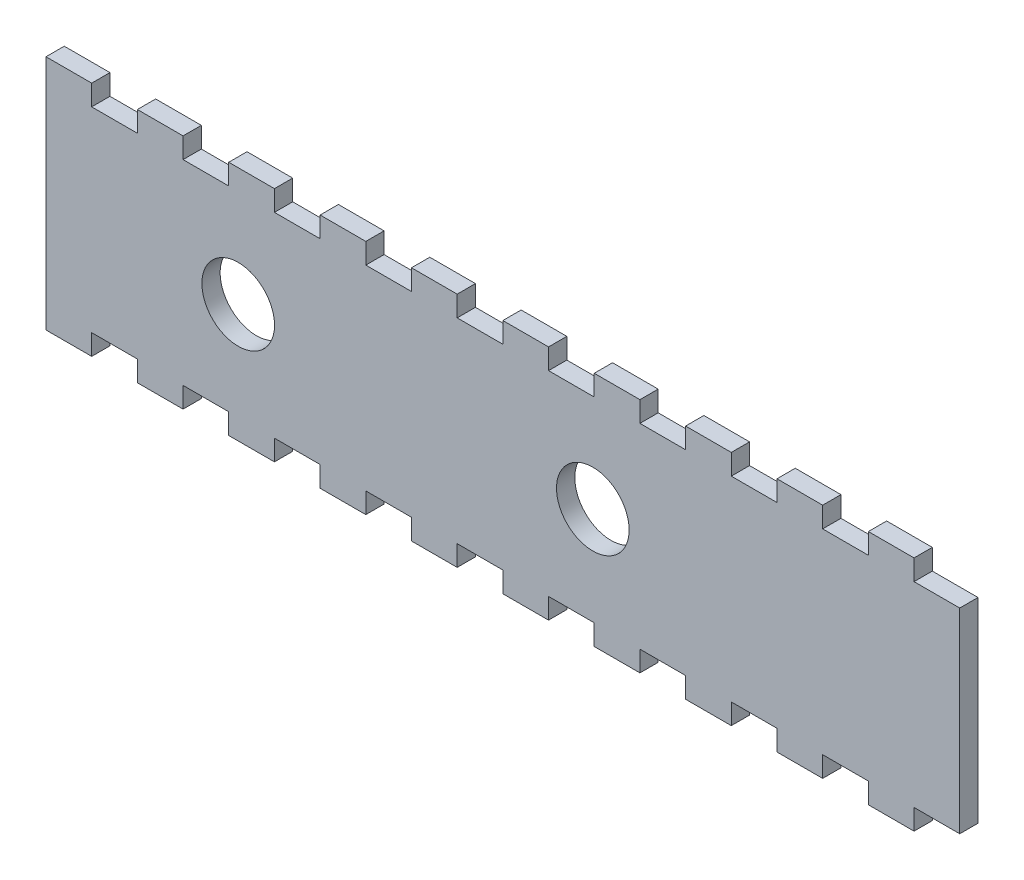
SolidWorks part; units mm, degrees
ref_plane "Front Plane" through (0, 0, 0) normal (0, 0, 1) x (1, 0, 0)
ref_plane "Top Plane" through (0, 0, 0) normal (0, 1, 0) x (1, 0, 0)
ref_plane "Right Plane" through (0, 0, 0) normal (1, 0, 0) x (0, 0, -1)
sketch "Sketch1" plane through (0, 0, 0) normal (0, 0, 1) x (1, 0, 0)
  line L0 (0, 10.7) -> (100, 10.7) construction
  line L1 (0, 0) -> (100, 0)
  line L2 (0, 0) -> (0, 21.4)
  line L3 (0, 21.4) -> (100, 21.4)
  line L4 (100, 0) -> (100, 21.4)
  line L5 (0, 21.4) -> (0, 23.65)
  line L6 (0, 23.65) -> (5, 23.65)
  line L7 (5, 23.65) -> (5, 21.4)
  line L8 (10, 23.65) -> (15, 23.65)
  line L9 (15, 23.65) -> (15, 21.4)
  line L10 (10, 21.4) -> (10, 23.65)
  line L11 (20, 23.65) -> (25, 23.65)
  line L12 (25, 23.65) -> (25, 21.4)
  line L13 (20, 21.4) -> (20, 23.65)
  line L14 (30, 23.65) -> (35, 23.65)
  line L15 (35, 23.65) -> (35, 21.4)
  line L16 (30, 21.4) -> (30, 23.65)
  line L17 (40, 23.65) -> (45, 23.65)
  line L18 (45, 23.65) -> (45, 21.4)
  line L19 (40, 21.4) -> (40, 23.65)
  line L20 (50, 23.65) -> (55, 23.65)
  line L21 (55, 23.65) -> (55, 21.4)
  line L22 (50, 21.4) -> (50, 23.65)
  line L23 (60, 23.65) -> (65, 23.65)
  line L24 (65, 23.65) -> (65, 21.4)
  line L25 (60, 21.4) -> (60, 23.65)
  line L26 (70, 23.65) -> (75, 23.65)
  line L27 (75, 23.65) -> (75, 21.4)
  line L28 (70, 21.4) -> (70, 23.65)
  line L29 (80, 23.65) -> (85, 23.65)
  line L30 (85, 23.65) -> (85, 21.4)
  line L31 (80, 21.4) -> (80, 23.65)
  line L32 (90, 23.65) -> (95, 23.65)
  line L33 (95, 23.65) -> (95, 21.4)
  line L34 (90, 21.4) -> (90, 23.65)
  line L35 (0, 0) -> (0, -2.25)
  line L36 (0, -2.25) -> (5, -2.25)
  line L37 (5, -2.25) -> (5, 0)
  line L38 (10, -2.25) -> (15, -2.25)
  line L39 (15, -2.25) -> (15, 0)
  line L40 (10, 0) -> (10, -2.25)
  line L41 (20, -2.25) -> (25, -2.25)
  line L42 (25, -2.25) -> (25, 0)
  line L43 (20, 0) -> (20, -2.25)
  line L44 (30, -2.25) -> (35, -2.25)
  line L45 (35, -2.25) -> (35, 0)
  line L46 (30, 0) -> (30, -2.25)
  line L47 (40, -2.25) -> (45, -2.25)
  line L48 (45, -2.25) -> (45, 0)
  line L49 (40, 0) -> (40, -2.25)
  line L50 (50, -2.25) -> (55, -2.25)
  line L51 (55, -2.25) -> (55, 0)
  line L52 (50, 0) -> (50, -2.25)
  line L53 (60, -2.25) -> (65, -2.25)
  line L54 (65, -2.25) -> (65, 0)
  line L55 (60, 0) -> (60, -2.25)
  line L56 (70, -2.25) -> (75, -2.25)
  line L57 (75, -2.25) -> (75, 0)
  line L58 (70, 0) -> (70, -2.25)
  line L59 (80, -2.25) -> (85, -2.25)
  line L60 (85, -2.25) -> (85, 0)
  line L61 (80, 0) -> (80, -2.25)
  line L62 (90, -2.25) -> (95, -2.25)
  line L63 (95, -2.25) -> (95, 0)
  line L64 (90, 0) -> (90, -2.25)
  circle A0 centre (21.0349, 10.7) radius 3.975
  circle A1 centre (59.8449, 10.7) radius 3.975
  dimension "D3" = 7.95
  dimension "D4" = 7.95
  dimension "D5" = 38.81
  dimension "D1" = 21.4
  dimension "D2" = 100
  dimension "D6" = 2.25
  dimension "D7" = 5
  dimension "D9" = 5
  dimension "D10" = 2.25
  dimension "D8" = 10
  dimension "D11" = 10
extrude "Boss-Extrude2" add sketch "Sketch1" along normal blind 2 contours L2 L0 A0 A1 L4 L3 | L0 L2 L1 L4 A1 A0 region at (50.4651, 16.2282, 0) region at (50.4651, 5.1718, 0)
extrude "Boss-Extrude4" add sketch "Sketch1<6>" along normal blind 2 contours L36 L37 L1 L35 | L1 L40 L38 L39 | L1 L64 L62 L63 | L1 L61 L59 L60 | L1 L58 L56 L57 | L1 L43 L41 L42 | L1 L46 L44 L45 | L1 L49 L47 L48 | L1 L52 L50 L51 | L1 L55 L53 L54 | L7 L6 L5 L3 | L10 L3 L9 L8 | L13 L3 L12 L11 | L16 L3 L15 L14 | L19 L3 L18 L17 | L22 L3 L21 L20 | L25 L3 L24 L23 | L28 L3 L27 L26 | L34 L3 L33 L32 | L31 L3 L30 L29 region at (2.5, -1.125, 0) region at (2.5, 22.525, 0) region at (12.5, -1.125, 0) region at (12.5, 22.525, 0) region at (22.5, -1.125, 0) region at (22.5, 22.525, 0) region at (32.5, -1.125, 0) region at (32.5, 22.525, 0) region at (42.5, -1.125, 0) region at (42.5, 22.525, 0) region at (52.5, -1.125, 0) region at (52.5, 22.525, 0) region at (62.5, -1.125, 0) region at (62.5, 22.525, 0) region at (72.5, -1.125, 0) region at (72.5, 22.525, 0) region at (82.5, -1.125, 0) region at (82.5, 22.525, 0) region at (92.5, -1.125, 0) region at (92.5, 22.525, 0)
sketch "Sketch1<6>" plane through (0, 0, 0) normal (0, 0, 1) x (1, 0, 0) same geometry as "Sketch1"
